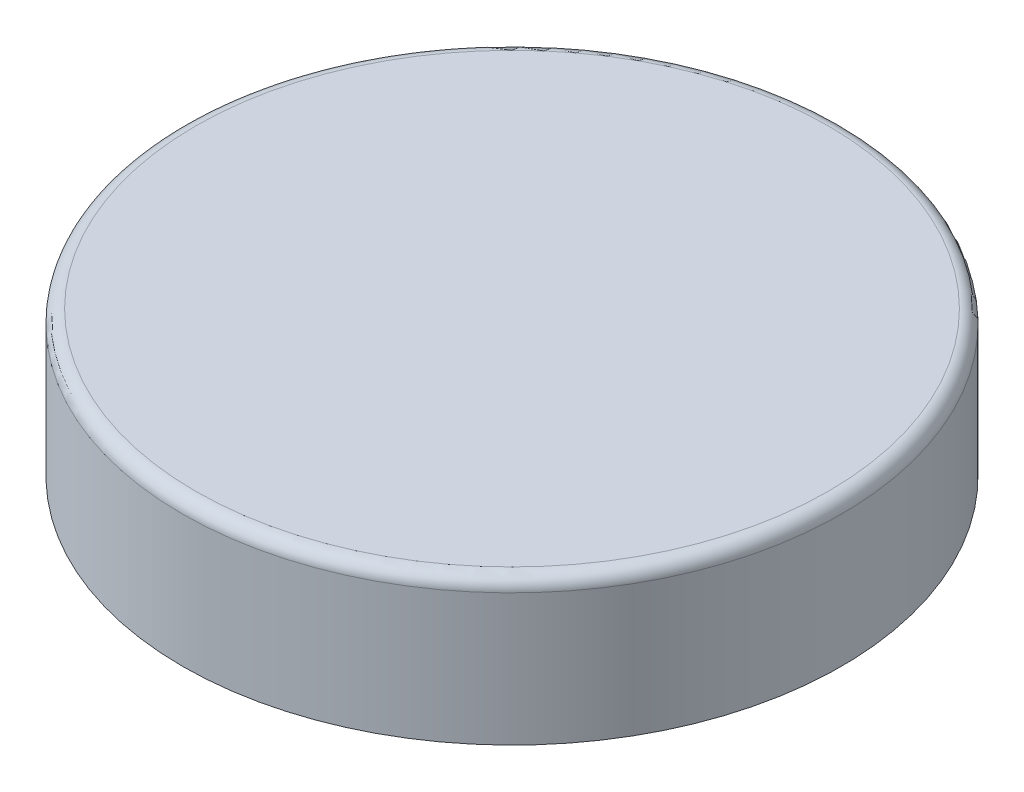
SolidWorks part; units mm, degrees
ref_plane "Front Plane" through (0, 0, 0) normal (0, 0, 1) x (1, 0, 0)
ref_plane "Top Plane" through (0, 0, 0) normal (0, 1, 0) x (1, 0, 0)
ref_plane "Right Plane" through (0, 0, 0) normal (1, 0, 0) x (0, 0, -1)
sketch "Sketch1" plane through (0, 0, 0) normal (0, 1, 0) x (1, 0, 0)
  circle A0 centre (0, 0) radius 25
  dimension "D1" = 50
extrude "Boss-Extrude1" add sketch "Sketch1" along normal blind 11
fillet "Fillet1" radius 1 1 edges at (0, 11, 25)
shell "Shell1" thickness 1 removed face at (0, 0, 25)
